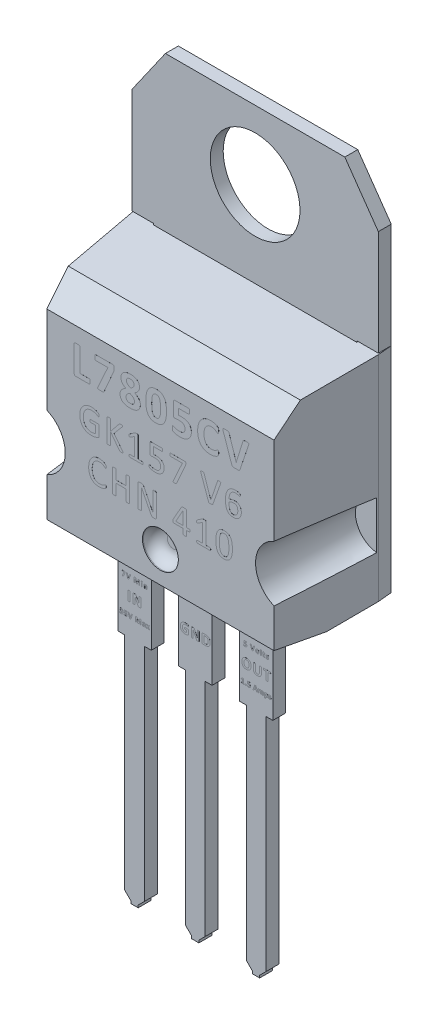
SolidWorks part; units mm, degrees
material "6061-T6 (SS)"
ref_plane "Front Plane" through (0, 0, 0) normal (0, 0, 1) x (1, 0, 0)
ref_plane "Top Plane" through (0, 0, 0) normal (0, 1, 0) x (1, 0, 0)
ref_plane "Right Plane" through (0, 0, 0) normal (1, 0, 0) x (0, 0, -1)
sketch "Sketch1" plane through (0, 0, 0) normal (1, 0, 0) x (0, 0, -1)
  line L0 (-0.27, 0) -> (0.27, 0) construction
  line L1 (0.27, 0) -> (2.77, 0) construction
  line L2 (2.77, 0) -> (2.77, 0.2628) construction
  line L3 (2.77, 0.2628) -> (0.27, 0)
  line L4 (2.77, 0.2628) -> (2.77, 9.2)
  line L5 (-0.27, 0) -> (-1.73, 0) construction
  line L6 (-1.73, 0) -> (-1.73, 0.2102) construction
  line L7 (0.27, 0) -> (-1.73, 0.2102)
  line L8 (-1.73, 0.2102) -> (-1.73, 7.8321)
  line L9 (2.77, 9.2) -> (-0.73, 8.8321)
  line L10 (-0.73, 8.8321) -> (-1.73, 8.727) construction
  line L11 (-1.73, 8.727) -> (-1.73, 7.8321) construction
  line L12 (-1.73, 7.8321) -> (-0.73, 8.8321)
  line L13 (2.77, 9.2) -> (-1.73, 9.2) construction
  line L14 (-1.73, 9.2) -> (-1.73, 8.727) construction
  line L15 (-0.73, 8.8321) -> (-0.73, 9.2) construction
  dimension "D1" = 0.54
  dimension "D2" = 2.5
  dimension "D3" = 9.2
  dimension "D4" = 6
  dimension "D5" = 4.5
  dimension "D6" = 6
  dimension "D7" = 45
  dimension "D8" = 3.5
extrude "Boss-Extrude1" add sketch "Sketch1" along normal mid plane 10.3
sketch "Sketch2" plane through (0, 0, 0) normal (0, 1, 0) x (1, 0, 0)
  line L0 (0, 0) -> (0, 2.77) construction
  line L1 (5.15, 2.77) -> (-5.15, 2.77) construction
  line L2 (-5.15, 2.77) -> (5.15, 2.77) construction
  line L3 (5.15, 2.77) -> (5.15, 2.23) construction
  line L4 (-5.15, 2.77) -> (-5.15, 2.23) construction
  line L5 (0, 0) -> (0, -1.73) construction
  line L6 (5.15, -1.73) -> (-5.15, -1.73) construction
  line L7 (-4.75, -1.73) -> (4.75, -1.73) construction
  line L8 (-4.75, -1.73) -> (-5.15, 2.23)
  line L9 (4.75, -1.73) -> (5.15, 2.23)
  line L10 (-4.75, -1.73) -> (-5.15, -1.73)
  line L11 (-5.15, -1.73) -> (-5.15, 2.23)
  line L12 (4.75, -1.73) -> (5.15, -1.73)
  line L13 (5.15, -1.73) -> (5.15, 2.23)
  dimension "D1" = 0.54
  dimension "D2" = 9.5
extrude "Cut-Extrude1" cut sketch "Sketch2" along normal through all
sketch "Sketch3" plane through (0, 0, -2.77) normal (0, 0, -1) x (-1, 0, 0)
  line L0 (0, 0) -> (0, 2.75) construction
  line L1 (-5.15, 9.2) -> (5.15, 9.2) construction
  line L2 (-4.25, 9.2) -> (4.25, 9.2)
  line L3 (-4.25, 9.2) -> (-4.25, 2.75)
  line L4 (-4.25, 2.75) -> (4.25, 2.75)
  line L5 (4.25, 9.2) -> (4.25, 2.75)
  dimension "D1" = 8.5
  dimension "D2" = 2.75
extrude "Cut-Extrude2" cut sketch "Sketch3" against normal blind 0.54
sketch "Sketch4" plane through (0, 0, -2.23) normal (0, 0, -1) x (-1, 0, 0)
  line L0 (-4.25, 2.75) -> (4.25, 2.75)
  line L1 (4.25, 2.75) -> (4.25, 9.2)
  line L2 (4.25, 9.2) -> (5.15, 9.2)
  line L3 (5.15, 9.2) -> (5.15, 13.6)
  line L4 (-4.25, 2.75) -> (-4.25, 9.2)
  line L5 (-4.25, 9.2) -> (-5.15, 9.2)
  line L6 (-5.15, 9.2) -> (-5.15, 13.6)
  line L7 (0, 0) -> (0, 2.75) construction
  line L8 (0, 2.75) -> (0, 12.73) construction
  line L9 (0, 12.73) -> (0, 15.6) construction
  line L10 (-3.75, 15.6) -> (3.75, 15.6)
  line L11 (-3.75, 15.6) -> (-5.15, 13.6)
  line L12 (3.75, 15.6) -> (5.15, 13.6)
  line L13 (-3.75, 15.6) -> (-5.15, 15.6) construction
  line L14 (-5.15, 15.6) -> (-5.15, 13.6) construction
  line L15 (3.75, 15.6) -> (5.15, 15.6) construction
  line L16 (5.15, 15.6) -> (5.15, 13.6) construction
  circle A0 centre (0, 12.73) radius 1.875
  point P21 (0, 14.605)
  dimension "D5" = 3.75
  dimension "D1" = 7.5
  dimension "D2" = 15.6
  dimension "D3" = 2
  dimension "D4" = 2.87
  dimension "D6" = 0.995
extrude "Boss-Extrude2" add sketch "Sketch4" along normal blind 0.54 separate body
sketch "Sketch5" plane through (0, 0, 0) normal (0, 0, 1) x (1, 0, 0)
  line L0 (0, 2.75) -> (0, -13.4) construction
  line L1 (4.25, 2.75) -> (-4.25, 2.75) construction
  line L2 (0, 2.75) -> (0, 5) construction
  line L3 (-0.15, -13.4) -> (0.15, -13.4)
  line L4 (0.15, -13.4) -> (0.15, -13.3)
  line L5 (-0.15, -13.4) -> (-0.15, -13.3)
  line L6 (0.15, -13.4) -> (0.41, -13.4) construction
  line L7 (-0.15, -13.4) -> (-0.41, -13.4) construction
  line L8 (0.41, -13.4) -> (0.41, -13.04) construction
  line L9 (0.41, -13.04) -> (0.15, -13.3)
  line L10 (-0.41, -13.4) -> (-0.41, -13.04) construction
  line L11 (-0.41, -13.04) -> (-0.15, -13.3)
  line L12 (0, 5) -> (0, 12.73) construction
  line L13 (0, 12.73) -> (0, 15.6) construction
  line L14 (-3.75, 15.6) -> (3.75, 15.6) construction
  line L15 (0.41, -13.04) -> (0.41, -3.8)
  line L16 (0.41, -3.8) -> (0.7, -3.8)
  line L17 (0.7, -3.8) -> (0.7, -1.2)
  line L18 (0.7, -1.2) -> (0.7, -1) construction
  line L19 (0.7, -1) -> (0.5, -1) construction
  line L20 (0.5, -1) -> (0.7, -1.2)
  line L21 (0.5, 5) -> (-0.5, 5)
  line L22 (0.5, 5) -> (0.5, -1)
  line L23 (-0.5, 5) -> (-0.5, -1)
  line L24 (-0.41, -13.04) -> (-0.41, -3.8)
  line L25 (0.41, -3.8) -> (0, -3.8) construction
  line L26 (0, -3.8) -> (-0.41, -3.8) construction
  line L27 (-0.41, -3.8) -> (-0.7, -3.8)
  line L28 (-0.7, -3.8) -> (-0.7, -1.2)
  line L29 (-0.5, -1) -> (-0.7, -1) construction
  line L30 (-0.7, -1) -> (-0.7, -1.2) construction
  line L31 (-0.5, -1) -> (-0.7, -1.2)
  line L32 (0.5, -1) -> (0, -1) construction
  line L33 (0, -1) -> (-0.5, -1) construction
  dimension "D1" = 5
  dimension "D2" = 0.3
  dimension "D3" = 0.82
  dimension "D4" = 45
  dimension "D5" = 0.1
  dimension "D6" = 29
  dimension "D7" = 1
  dimension "D8" = 45
  dimension "D9" = 1.4
  dimension "D10" = 3.8
  dimension "D11" = 1
  dimension "D12" = 13.4
  dimension "D13" = 16.53
  dimension "D14" = 2.87
extrude "Boss-Extrude3" add sketch "Sketch5" along normal mid plane 0.54
pattern_linear "LPattern2" count 2 spacing 2.54 along (1, 0, 0) count 2 spacing 2.54 along (-1, 0, 0) of "Boss-Extrude3"
sketch "Sketch6" plane through (0, 0, 1.73) normal (0, 0, 1) x (1, 0, 0)
  line L0 (0, 0) -> (0, 1.5) construction
  line L1 (0, 1.5) -> (0, 3) construction
  line L2 (0, 3) -> (0, 12.73) construction
  line L3 (-5.25, 3) -> (5.25, 3) construction
  circle A0 centre (0, 1.5) radius 0.75
  circle A1 centre (5.25, 3) radius 1 construction
  circle A2 centre (-5.25, 3) radius 1 construction
  dimension "D1" = 1.5
  dimension "D2" = 1.5
  dimension "D4" = 10.5
  dimension "D5" = 2
  dimension "D3" = 3
extrude "Cut-Extrude3" cut sketch "Sketch6" against normal blind 0.54
fillet "Fillet1" radius 0.5 1 edges at (0.75, 1.5, 1.19)
ref_plane "Plane1" through (0, 0, -2.17) normal (0, 0, -1) x (-1, 0, 0)
sketch "Sketch7" plane through (0, 0, -2.17) normal (0, 0, -1) x (-1, 0, 0)
  circle A0 centre (-5.25, 3) radius 1 construction
  circle A1 centre (5.25, 3) radius 1 construction
  circle A2 centre (-5.25, 3) radius 1
  circle A3 centre (5.25, 3) radius 1
extrude "Cut-Extrude9" cut sketch "Sketch7" against normal up to surface (3.9 mm away) draft 4
sketch "Sketch8" plane through (0, -13.4, 0) normal (0, -1, 0) x (1, 0, 0)
  line L0 (-2.54, 0) -> (2.54, 0) construction
  circle A0 centre (0, 0) radius 0.1
  circle A1 centre (-2.54, 0) radius 0.1
  circle A2 centre (2.54, 0) radius 0.1
  dimension "D1" = 0.2
  dimension "D2" = 5.08
extrude "Cut-Extrude10" cut sketch "Sketch8" against normal blind 0.01
sketch "Sketch9" plane through (0, 0, 1.73) normal (0, 0, 1) x (1, 0, 0)
  line L0 (-4.75, 6) -> (4.75, 6) construction
  line L1 (-4.75, 7.8321) -> (-4.75, 4.1704) construction
  line L2 (4.75, 7.8321) -> (4.75, 4.1704) construction
  line L3 (0, 0) -> (0, 2.5) construction
  line L4 (0, 2.5) -> (0, 4.2) construction
  line L5 (0, 4.2) -> (0, 6) construction
  line L6 (-4.75, 4.2) -> (4.75, 4.2) construction
  line L7 (-4.75, 2.5) -> (4.75, 2.5) construction
  text T0 "L7805CV" font "Calibri" height 1.2
  text T1 "GK157 V6" font "Calibri" height 1
  text T2 "CHN 410" font "Calibri" height 1
  dimension "D1" = 2.5
  dimension "D2" = 4.2
  dimension "D3" = 6
extrude "Boss-Extrude4" add sketch "Sketch9" along normal blind 0.001
sketch "Sketch10" plane through (0, 0, 0.27) normal (0, 0, 1) x (1, 0, 0)
  line L0 (-0.7, -2.5) -> (0.7, -2.5) construction
  line L1 (-0.7, -1.2) -> (-0.7, -3.8) construction
  line L2 (0.7, -3.8) -> (0.7, -1.2) construction
  line L3 (0.7, -2.5) -> (1.84, -2.5) construction
  line L4 (1.84, -1.2) -> (1.84, -3.8) construction
  line L5 (1.84, -2.5) -> (3.24, -2.5) construction
  line L6 (3.24, -3.8) -> (3.24, -1.2) construction
  line L7 (-0.7, -2.5) -> (-1.84, -2.5) construction
  line L8 (-1.84, -3.8) -> (-1.84, -1.2) construction
  line L9 (-1.84, -2.5) -> (-3.24, -2.5) construction
  line L10 (-3.24, -1.2) -> (-3.24, -3.8) construction
  line L11 (-3.24, -1.7) -> (-1.84, -1.7) construction
  line L12 (-1.84, -1.7) -> (-0.7, -1.7) construction
  line L13 (-0.7, -1.7) -> (0.7, -1.7) construction
  line L14 (0.7, -1.7) -> (1.84, -1.7) construction
  line L15 (1.84, -1.7) -> (3.24, -1.7) construction
  line L16 (-3.24, -3.1) -> (-1.84, -3.1) construction
  line L17 (-1.84, -3.1) -> (-0.7, -3.1) construction
  line L18 (-0.7, -3.1) -> (0.7, -3.1) construction
  line L19 (0.7, -3.1) -> (1.84, -3.1) construction
  line L20 (1.84, -3.1) -> (3.24, -3.1) construction
  text T0 "GND" font "Calibri" height 0.4
  text T1 "IN" font "Calibri" height 0.4
  text T2 "OUT" font "Calibri" height 0.4
  text T3 "7V Min" font "Calibri" height 0.2
  text T4 "35V Max" font "Calibri" height 0.2
  text T5 "5 Volts" font "Calibri" height 0.2
  text T6 "1.5 Amps" font "Calibri" height 0.2
  dimension "D1" = 0.6
  dimension "D2" = 0.8
extrude "Boss-Extrude5" add sketch "Sketch10" along normal blind 0.001
